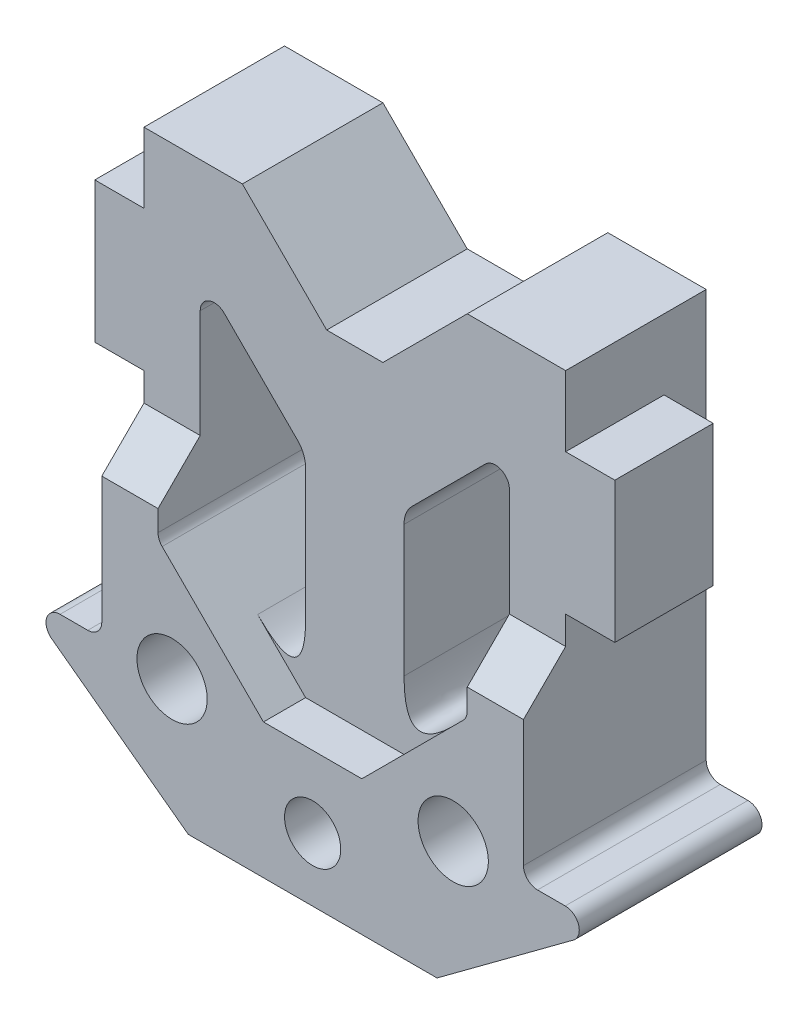
SolidWorks part; units mm, degrees
note: The reader was unsure of these and kept them because the rebuilt part matched: shared geometry of "Esquisse4<4>".
ref_plane "Plan de face" through (0, 0, 0) normal (0, 0, 1) x (1, 0, 0)
ref_plane "Plan de dessus" through (0, 0, 0) normal (0, 1, 0) x (1, 0, 0)
ref_plane "Plan de droite" through (0, 0, 0) normal (1, 0, 0) x (0, 0, -1)
sketch "Esquisse1" plane through (0, 0, 0) normal (0, 0, 1) x (1, 0, 0)
  line L0 (-16, 6) -> (-8, 6)
  line L1 (-8, 6) -> (-2, 0)
  line L2 (-2, 0) -> (2, 0)
  line L3 (16, -24) -> (16, 6)
  line L4 (21, -24) -> (16, -24)
  line L5 (7.5, -34) -> (21, -24)
  line L6 (7.5, -34) -> (-7.5, -34)
  line L7 (-7.5, -34) -> (-21, -24)
  line L8 (-21, -24) -> (-16, -24)
  line L9 (-16, -24) -> (-16, 6)
  line L10 (2, 0) -> (8, 6)
  line L11 (8, 6) -> (16, 6)
  line L12 (0, -1000) -> (0, 49000) construction
  line L13 (-18.5, 1) -> (-18.5, -9)
  line L14 (16, 1) -> (18.5, 1)
  line L15 (16, 1) -> (16, -9)
  line L16 (16, -9) -> (18.5, -9)
  line L17 (18.5, 1) -> (18.5, -9)
  line L18 (-16, -9) -> (-18.5, -9)
  line L19 (-16, 1) -> (-16, -9)
  line L20 (-16, 1) -> (-18.5, 1)
  point P17 (0, -34)
  dimension "D1" = 5
  dimension "D2" = 135
  dimension "D3" = 8
  dimension "D4" = 15
  dimension "D5" = 10
  dimension "D6" = 32
  dimension "D7" = 8
  dimension "D8" = 4
  dimension "D9" = 30
  dimension "D10" = 2.5
  dimension "D11" = 10
  dimension "D12" = 15
extrude "Boss.-Extru.1" add sketch "Esquisse1" along normal blind 7 contours L6 L12 L2 L1 L0 L9 L8 L7 | L12 L6 L5 L4 L3 L11 L10 L2 | L17 L14 L3 L16 | L9 L20 L13 L18
sketch "Esquisse2" plane through (0, 0, 7) normal (0, 0, 1) x (1, 0, 0)
  line L0 (-16, -14) -> (16, -14)
  line L20 (-7.5, -34) -> (7.5, -34)
  line L21 (7.5, -34) -> (21, -24)
  line L22 (21, -24) -> (16, -24)
  line L23 (16, -24) -> (16, -9)
  line L24 (16, -9) -> (18.5, -9)
  line L25 (18.5, -9) -> (18.5, 1)
  line L26 (18.5, 1) -> (16, 1)
  line L27 (16, 1) -> (16, 6)
  line L28 (16, 6) -> (8, 6)
  line L29 (8, 6) -> (2, 0)
  line L30 (2, 0) -> (-2, 0)
  line L31 (-2, 0) -> (-8, 6)
  line L32 (-8, 6) -> (-16, 6)
  line L33 (-16, 6) -> (-16, 1)
  line L34 (-16, 1) -> (-18.5, 1)
  line L35 (-18.5, 1) -> (-18.5, -9)
  line L36 (-18.5, -9) -> (-16, -9)
  line L37 (-16, -9) -> (-16, -24)
  line L38 (-16, -24) -> (-21, -24)
  line L39 (-21, -24) -> (-7.5, -34)
  line L40 (-7.5, -34) -> (7.5, -34)
  line L41 (7.5, -34) -> (21, -24)
  line L42 (21, -24) -> (16, -24)
  line L43 (16, -24) -> (16, -9)
  line L44 (16, -9) -> (18.5, -9)
  line L45 (18.5, -9) -> (18.5, 1)
  line L46 (18.5, 1) -> (16, 1)
  line L47 (16, 1) -> (16, 6)
  line L48 (16, 6) -> (8, 6)
  line L49 (8, 6) -> (2, 0)
  line L50 (2, 0) -> (-2, 0)
  line L51 (-2, 0) -> (-8, 6)
  line L52 (-8, 6) -> (-16, 6)
  line L53 (-16, 6) -> (-16, 1)
  line L54 (-16, 1) -> (-18.5, 1)
  line L55 (-18.5, 1) -> (-18.5, -9)
  line L56 (-18.5, -9) -> (-16, -9)
  line L57 (-16, -9) -> (-16, -24)
  line L58 (-16, -24) -> (-21, -24)
  line L59 (-21, -24) -> (-7.5, -34)
  dimension "D2" = 20
  dimension "D1" = 0
extrude "Boss.-Extru.2" add sketch "Esquisse2" along normal blind 3 and the other way offset from surface (10 mm away) 3 contours L58 L59 L40 L41 L42 L43 L0 L57 other way up to face at (0, -8.6, 0)
sketch "Esquisse3" plane through (0, 0, -3) normal (0, 0, -1) x (-1, 0, 0)
  line L0 (-11, -0.8995) -> (-3.5, -8.3995)
  line L1 (-3.5, -8.3995) -> (-3.5, -23.3995)
  line L2 (-3.5, -23.3995) -> (-11, -15.8995)
  line L3 (-11, -15.8995) -> (-11, -0.8995)
  line L4 (0, -1000) -> (0, 49000) construction
  line L5 (11, -15.8995) -> (11, -0.8995)
  line L6 (3.5, -23.3995) -> (11, -15.8995)
  line L7 (3.5, -8.3995) -> (3.5, -23.3995)
  line L8 (11, -0.8995) -> (3.5, -8.3995)
  line L14 (-2, 0) -> (-8, 6) construction
  line L15 (-16, 1) -> (-16, 6) construction
  dimension "D1" = 7
  dimension "D2" = 5
  dimension "D3" = 7
  dimension "D4" = 15
extrude "Enlèv. mat.-Extru.1" cut sketch "Esquisse3" against normal up to next
sketch "Esquisse4" plane through (0, 0, -3) normal (0, 0, -1) x (-1, 0, 0)
  line L1 (-3.5, -14) -> (3.5, -14)
  line L2 (-3.5, -14) -> (-3.5, -23.3995)
  line L3 (-3.5, -23.3995) -> (3.5, -23.3995)
  line L4 (3.5, -14) -> (3.5, -23.3995)
extrude "Enlèv. mat.-Extru.4" cut sketch "Esquisse4<4>" against normal up to surface (3 mm away) up to face at (0, -4.6082, 0)
sketch "Esquisse4<4>" plane through (0, 0, -3) normal (0, 0, -1) x (-1, 0, 0) same geometry as "Esquisse4"
extrude "Enlèv. mat.-Extru.2" cut sketch "Esquisse4" along normal up to surface (3 mm away) from surface at -13 up to face at (0, -4.6082, 7) starting at face at (0, -20.4124, 10)
chamfer "Chanfrein1" distance 3 angle 45 4 edges at (-13.5, -14, 0) (-13.5, -14, 7) (13.5, -14, 0) (13.5, -14, 7)
fillet "Congé1" radius 1 6 edges at (11, -15.8995, 3.5) (-11, -15.8995, 3.5) (11, -0.8995, 3.5) (-11, -0.8995, 3.5) (21, -24, 3.5) (-21, -24, 3.5)
sketch "Esquisse5" plane through (0, -34, 0) normal (0, -1, 0) x (1, 0, 0)
  line L0 (-7.5, 10) -> (7.5, -3) construction
  circle A0 centre (0, 3.5) radius 4.8
  dimension "D1" = 9.6
extrude "Enlèv. mat.-Extru.5" cut sketch "Esquisse5" against normal blind 1
sketch "Esquisse6" plane through (0, 0, 10) normal (0, 0, 1) x (1, 0, 0)
  line L0 (0, -1000) -> (0, 49000) construction
  line L1 (-7.5, -34) -> (7.5, -34) construction
  circle A0 centre (-10, -24) radius 2.5
  circle A1 centre (0, -28.5) radius 2
  circle A2 centre (10, -24) radius 2.5
  dimension "D1" = 5
  dimension "D2" = 4
  dimension "D3" = 5.5
  dimension "D4" = 10
  dimension "D5" = 10
extrude "Enlèv. mat.-Extru.6" cut sketch "Esquisse6" against normal through all
chamfer "Chanfrein2" distance 1 angle 45 2 edges at (0, -34, -3) (0, -34, 10)
sketch "Эскиз1" plane through (16, 0, 0) normal (1, 0, 0) x (0, 0, -1)
  line L0 (0, 1) -> (0, 6) construction
  line L1 (0, 6) -> (-7, 6) construction
  line L2 (-7, 6) -> (-7, 1) construction
  line L3 (-7, 1) -> (0, 1) construction
  line L4 (-10, -24) -> (3, -24) construction
  line L5 (3, -24) -> (3, -14) construction
  line L6 (3, -14) -> (0, -11) construction
  line L7 (0, -11) -> (0, -9) construction
  line L8 (0, -9) -> (-7, -9) construction
  line L9 (-7, -9) -> (-7, -11) construction
  line L10 (-7, -11) -> (-10, -14) construction
  line L11 (-10, -14) -> (-10, -24) construction
  line L12 (0, 1) -> (0, 6)
  line L13 (0, 6) -> (-7, 6)
  line L14 (-7, 6) -> (-7, 1)
  line L15 (-7, 1) -> (0, 1)
  line L16 (-10, -24) -> (3, -24)
  line L17 (3, -24) -> (3, -14)
  line L18 (3, -14) -> (0, -11)
  line L19 (0, -11) -> (0, -9)
  line L20 (0, -9) -> (-7, -9)
  line L21 (-7, -9) -> (-7, -11)
  line L22 (-7, -11) -> (-10, -14)
  line L23 (-10, -14) -> (-10, -24)
extrude "Вырез-Вытянуть1" cut sketch "Эскиз1" against normal blind 1
sketch "Эскиз2" plane through (-16, 0, 0) normal (-1, 0, 0) x (0, 0, 1)
  line L0 (0, 6) -> (0, 1) construction
  line L1 (0, 1) -> (7, 1) construction
  line L2 (7, 1) -> (7, 6) construction
  line L3 (7, 6) -> (0, 6) construction
  line L4 (10, -24) -> (10, -14) construction
  line L5 (10, -14) -> (7, -11) construction
  line L6 (7, -11) -> (7, -9) construction
  line L7 (7, -9) -> (0, -9) construction
  line L8 (0, -9) -> (0, -11) construction
  line L9 (0, -11) -> (-3, -14) construction
  line L10 (-3, -14) -> (-3, -24) construction
  line L11 (-3, -24) -> (10, -24) construction
  line L12 (0, 6) -> (0, 1)
  line L13 (0, 1) -> (7, 1)
  line L14 (7, 1) -> (7, 6)
  line L15 (7, 6) -> (0, 6)
  line L16 (10, -24) -> (10, -14)
  line L17 (10, -14) -> (7, -11)
  line L18 (7, -11) -> (7, -9)
  line L19 (7, -9) -> (0, -9)
  line L20 (0, -9) -> (0, -11)
  line L21 (0, -11) -> (-3, -14)
  line L22 (-3, -14) -> (-3, -24)
  line L23 (-3, -24) -> (10, -24)
extrude "Вырез-Вытянуть2" cut sketch "Эскиз2" against normal blind 1
sketch "Эскиз4" plane through (0, 0, 0) normal (0, 0, -1) x (-1, 0, 0)
  line L0 (15, -14) -> (15, -11) construction
  line L1 (11, -11) -> (11, -14) construction
  line L2 (11, -14) -> (15, -14) construction
  line L3 (15, -11) -> (15, -9) construction
  line L7 (15, 1) -> (15, 6) construction
  line L8 (15, 6) -> (8, 6) construction
  line L9 (8, 6) -> (2, 0) construction
  line L10 (2, 0) -> (-2, 0) construction
  line L11 (-2, 0) -> (-8, 6) construction
  line L12 (-8, 6) -> (-15, 6) construction
  line L13 (-15, 6) -> (-15, 1) construction
  line L17 (-15, -9) -> (-15, -11) construction
  line L18 (-11, -11) -> (-11, -3.3137) construction
  line L19 (-9.2929, -2.6066) -> (-3.5, -8.3995) construction
  line L20 (-3.5, -8.3995) -> (-3.5, -23.3995) construction
  line L21 (-3.5, -23.3995) -> (3.5, -23.3995) construction
  line L22 (3.5, -23.3995) -> (3.5, -8.3995) construction
  line L23 (3.5, -8.3995) -> (9.2929, -2.6066) construction
  line L24 (11, -3.3137) -> (11, -11) construction
  line L25 (-15, -11) -> (-15, -14) construction
  line L26 (-15, -14) -> (-11, -14) construction
  line L27 (-11, -14) -> (-11, -11) construction
  line L28 (15, -14) -> (15, -11)
  line L29 (11, -11) -> (11, -14)
  line L30 (11, -14) -> (15, -14)
  line L31 (15, -11) -> (15, -9)
  line L35 (15, -9) -> (15, 6)
  line L36 (15, 6) -> (8, 6)
  line L37 (8, 6) -> (2, 0)
  line L38 (2, 0) -> (-2, 0)
  line L39 (-2, 0) -> (-8, 6)
  line L40 (-8, 6) -> (-15, 6)
  line L41 (-15, 6) -> (-15, -9)
  line L45 (-15, -9) -> (-15, -11)
  line L46 (-11, -11) -> (-11, -3.3137)
  line L47 (-9.2929, -2.6066) -> (-3.5, -8.3995)
  line L48 (-3.5, -8.3995) -> (-3.5, -23.3995)
  line L49 (-3.5, -23.3995) -> (3.5, -23.3995)
  line L50 (3.5, -23.3995) -> (3.5, -8.3995)
  line L51 (3.5, -8.3995) -> (9.2929, -2.6066)
  line L52 (11, -3.3137) -> (11, -11)
  line L53 (-15, -11) -> (-15, -14)
  line L54 (-15, -14) -> (-11, -14)
  line L55 (-11, -14) -> (-11, -11)
  arc A0 (-9.2929, -2.6066) -> (-11, -3.3137) centre (-10, -3.3137) ccw construction
  arc A1 (11, -3.3137) -> (9.2929, -2.6066) centre (10, -3.3137) ccw construction
  arc A2 (-9.2929, -2.6066) -> (-11, -3.3137) centre (-10, -3.3137) ccw
  arc A3 (11, -3.3137) -> (9.2929, -2.6066) centre (10, -3.3137) ccw
extrude "Бобышка-Вытянуть1" add sketch "Эскиз4" along normal up to surface (3 mm away) up to face at (7.5, -24, -3)
fillet "Скругление1" radius 3 2 edges at (-7.5, -34, 3.5) (7.5, -34, 3.5)
fillet "Скругление2" radius 1 2 edges at (-15, -24, 3.5) (15, -24, 3.5)
fillet "Скругление3" radius 2 2 edges at (3.5, -8.3995, 2) (-3.5, -8.3995, 2)
ref_plane "Плоскость1" through (3.5, -23.3995, 7) normal (0, 0, -1) x (-1, 0, 0)
fillet "Скругление4" radius 2 2 edges at (-3.5, -23.3995, 2) (3.5, -23.3995, 2)
sketch "Эскиз5" plane through (-15, 0, 0) normal (-1, 0, 0) x (0, 0, 1)
  circle A0 centre (-3.3903, -5.4121) radius 3
  dimension "D1" = 6
extrude "Вырез-Вытянуть3" cut sketch "Эскиз5" against normal up to surface (30 mm away)
